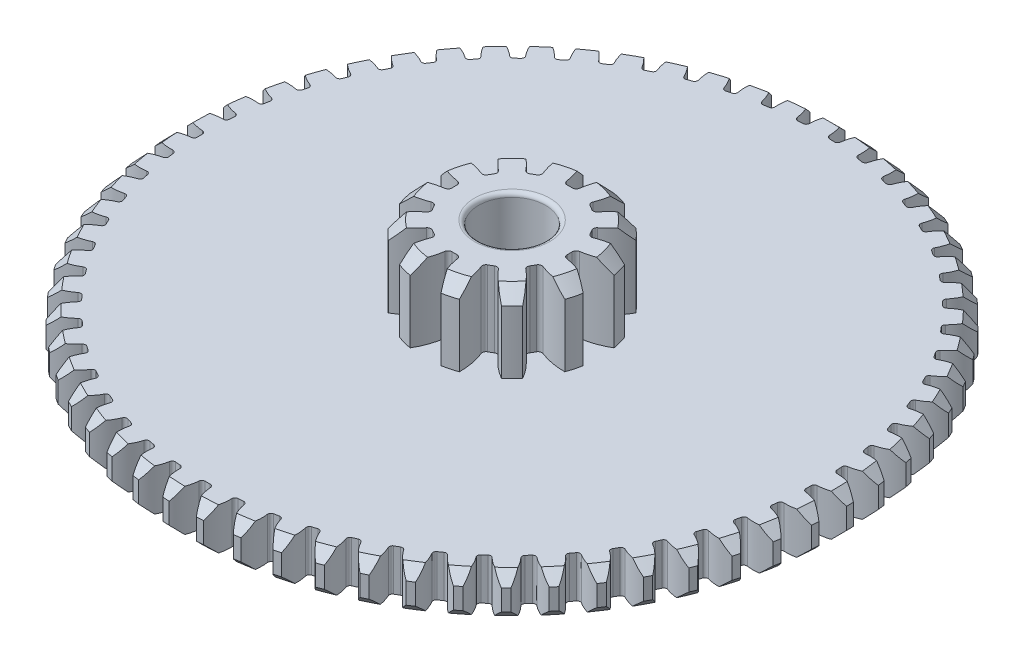
SolidWorks part; units mm, degrees
ref_plane "Front Plane" through (0, 0, 0) normal (0, 0, 1) x (1, 0, 0)
ref_plane "Top Plane" through (0, 0, 0) normal (0, 1, 0) x (1, 0, 0)
ref_plane "Right Plane" through (0, 0, 0) normal (1, 0, 0) x (0, 0, -1)
sketch "Sketch1" plane through (0, 0, 0) normal (0, 1, 0) x (1, 0, 0)
  circle A0 centre (0, 0) radius 1.8 construction
  circle A1 centre (0, 0) radius 2.1
  dimension "D1" = 3.6
  dimension "D2" = 4.2
extrude "Boss-Extrude1" add sketch "Sketch1" along normal blind 1.8
sketch "Sketch2" plane through (0, 1.8, 0) normal (0, 1, 0) x (1, 0, 0)
  line L0 (0, 0) -> (0, 2.1) construction
  line L1 (0, 0) -> (1.05, 1.8187) construction
  line L2 (0, 0) -> (0.5435, 2.0284) construction
  line L3 (0, 0) -> (-0.1405, 1.3728) construction
  line L4 (-0.2349, 1.7846) -> (0.2349, 1.7846) construction
  line L5 (0.2349, 1.7846) -> (0.6888, 1.663) construction
  line L6 (-0.3397, 2.0723) -> (0, 1.1391) construction
  circle A0 centre (0, 0) radius 1.5 construction
  circle A2 centre (0, 0) radius 2.1 construction
  arc A3 (-0.1405, 1.3728) -> (-0.3683, 2.0675) centre (-1.8457, 1.1983) ccw
  arc A4 (0.1405, 1.3728) -> (0.3683, 2.0675) centre (1.8457, 1.1983) cw
  circle A5 centre (0, 0) radius 1.8 construction
  arc A7 (0.1405, 1.3728) -> (-0.1405, 1.3728) centre (0, 0) ccw
  arc A8 (0.3683, 2.0675) -> (-0.3683, 2.0675) centre (0, 0) ccw
  dimension "D1" = 30
  dimension "D4" = 20
extrude "Cut-Extrude1" cut sketch "Sketch2" against normal up to next
fillet "Fillet1" radius 0.09 2 edges at (0.1405, 0.9, -1.3728) (-0.1405, 0.9, -1.3728)
chamfer "Chamfer1" distance 0.3 1 edges at (0, 1.8, 2.1)
pattern_circular "CirPattern1" count 12 over 360 about axis through (0, 1.8, 0) along (0, -1, 0) of "Cut-Extrude1", "Fillet1" reverse direction yes
sketch "Sketch3" plane through (0, 0, 0) normal (0, -1, 0) x (1, 0, 0)
  circle A0 centre (0, 0) radius 7.625 construction
  circle A1 centre (0, 0) radius 7.875
  dimension "D1" = 15.25
  dimension "D2" = 15.75
extrude "Boss-Extrude2" add sketch "Sketch3" along normal blind 1
sketch "Sketch4" plane through (0, -1, 0) normal (0, -1, 0) x (1, 0, 0)
  line L0 (0, 0) -> (0, 7.875) construction
  line L1 (0, 0) -> (0.8097, 7.8333) construction
  line L2 (0, 0) -> (0.4054, 7.8646) construction
  line L3 (-0.1316, 7.2738) -> (0, 0) construction
  line L4 (-0.1963, 7.6225) -> (0.1963, 7.6225) construction
  line L5 (0.1963, 7.6225) -> (0.5885, 7.6023) construction
  line L6 (-0.2863, 7.8698) -> (0, 7.0831) construction
  circle A0 centre (0, 0) radius 7.375 construction
  circle A2 centre (0, 0) radius 7.875 construction
  arc A3 (-0.3237, 7.8683) -> (-0.1316, 7.2738) centre (-1.2078, 7.2543) cw
  arc A4 (0.3237, 7.8683) -> (0.1316, 7.2738) centre (1.2078, 7.2543) ccw
  circle A5 centre (0, 0) radius 7.625 construction
  arc A6 (0.3237, 7.8683) -> (-0.3237, 7.8683) centre (0, 0) ccw
  arc A7 (0.1316, 7.2738) -> (-0.1316, 7.2738) centre (0, 0) ccw
  dimension "D4" = 20
  dimension "D1" = 5.902
  dimension "D2" = 0.5
extrude "Cut-Extrude2" cut sketch "Sketch4" against normal up to next
fillet "Fillet2" radius 0.075 2 edges at (0.1316, -0.5, 7.2738) (-0.1316, -0.5, 7.2738)
chamfer "Chamfer2" distance 0.25 2 edges at (0, 0, -7.875) (0, -1, -7.875)
pattern_circular "CirPattern2" count 61 over 360 about axis through (0, -1, 0) along (0, 1, 0) of "Cut-Extrude2", "Fillet2" reverse direction yes
sketch "Sketch5" plane through (0, 1.8, 0) normal (0, 1, 0) x (1, 0, 0)
  circle A0 centre (0, 0) radius 0.8
  dimension "D1" = 1.6
extrude "Cut-Extrude3" cut sketch "Sketch5" against normal through all
fillet "Fillet3" radius 0.1 2 edges at (0, 1.8, 0.8) (0, -1, 0.8)
equation "\"Module of small gear\"= 0.3"
equation "\"Number of teeth of small gear\"= 12"
equation "\"Pressure Angle\"= 20"
equation "\"D1@Sketch1\"=\"Module of small gear\" * \"Number of teeth of small gear\""
equation "\"D2@Sketch1\"=(\"Number of teeth of small gear\" + 2) * \"Module of small gear\""
equation "\"D1@Sketch2\"=360 / \"Number of teeth of small gear\""
equation "\"D2@Sketch2\"=\"Module of small gear\" * 2"
equation "\"D4@Sketch2\"=\"Pressure Angle\""
equation "\"D1@Fillet1\"=0.3 * \"Module of small gear\""
equation "\"D1@CirPattern1\"=\"Number of teeth of small gear\""
equation "\"D1@Chamfer1\"=\"Module of small gear\""
equation "\"Module of big gear\"= 0.25"
equation "\"Number of teeth of big gear\"= 61"
equation "\"D1@Sketch3\"=\"Module of big gear\" * \"Number of teeth of big gear\""
equation "\"D1@Sketch4\"=360 / \"Number of teeth of big gear\""
equation "\"D2@Sketch4\"=\"Module of big gear\" * 2"
equation "\"D4@Sketch4\"=\"Pressure Angle\""
equation "\"D1@Fillet2\"=0.3 * \"Module of big gear\""
equation "\"D1@CirPattern2\"=\"Number of teeth of big gear\""
equation "\"D1@Chamfer2\"=\"Module of big gear\""
